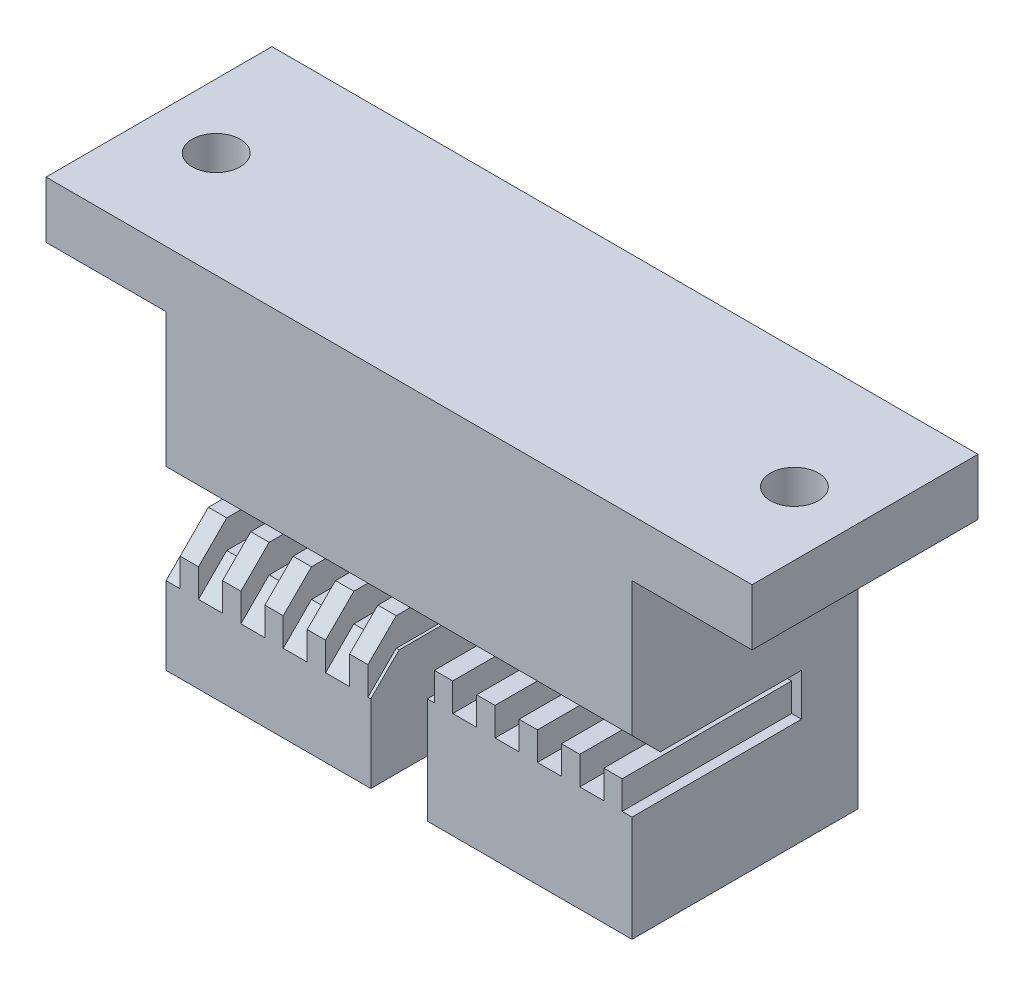
SolidWorks part; units mm, degrees
ref_plane "Front Plane" through (0, 0, 0) normal (0, 0, 1) x (1, 0, 0)
ref_plane "Top Plane" through (0, 0, 0) normal (0, 1, 0) x (1, 0, 0)
ref_plane "Right Plane" through (0, 0, 0) normal (1, 0, 0) x (0, 0, -1)
ref_plane "Plane1" through (0, 0, -1) normal (0, 0, -1) x (-1, 0, 0)
sketch "Sketch1" plane through (0, 0, -1) normal (0, 0, -1) x (-1, 0, 0)
  line L0 (0, 0) -> (50, 0)
  line L1 (50, 0) -> (50, 26)
  line L2 (50, 26) -> (0, 26)
  line L3 (0, 26) -> (0, 0)
extrude "Boss-Extrude1" add sketch "Sketch1" against normal blind 16
sketch "Sketch2" plane through (0, 0, -1) normal (0, 0, -1) x (-1, 0, 0)
  line L0 (41.5, 22) -> (41.5, 0)
  line L1 (41.5, 0) -> (50, 0)
  line L2 (50, 0) -> (50, 22)
  line L3 (50, 22) -> (41.5, 22)
extrude "Cut-Extrude1" cut sketch "Sketch2" against normal through all
sketch "Sketch3" plane through (0, 0, -1) normal (0, 0, -1) x (-1, 0, 0)
  line L0 (0, 0) -> (8.5, 0)
  line L1 (8.5, 0) -> (8.5, 22)
  line L2 (8.5, 22) -> (0, 22)
  line L3 (0, 22) -> (0, 0)
extrude "Cut-Extrude2" cut sketch "Sketch3" against normal through all
sketch "Sketch4" plane through (-41.5, 0, 0) normal (-1, 0, 0) x (0, 0, 1)
  line L0 (15, 10.5) -> (3, 10.5)
  line L1 (3, 10.5) -> (3, 0)
  line L2 (3, 0) -> (15, 0)
  line L3 (15, 0) -> (15, 10.5)
extrude "Cut-Extrude3" cut sketch "Sketch4" against normal through all
sketch "Sketch5" plane through (0, 0, 3) normal (0, 0, 1) x (1, 0, 0)
  line L0 (-23, 7.5) -> (-8.5, 7.5)
  line L1 (-8.5, 7.5) -> (-8.5, 0)
  line L2 (-8.5, 0) -> (-23, 0)
  line L3 (-23, 0) -> (-23, 7.5)
extrude "Boss-Extrude2" add sketch "Sketch5" along normal blind 12
sketch "Sketch6" plane through (0, 0, 3) normal (0, 0, 1) x (1, 0, 0)
  line L0 (-10.5, 9.5) -> (-9.2, 9.5)
  line L1 (-9.2, 9.5) -> (-9.2, 7.5)
  line L2 (-9.2, 7.5) -> (-10.5, 7.5)
  line L3 (-10.5, 7.5) -> (-10.5, 9.5)
extrude "Boss-Extrude3" add sketch "Sketch6" along normal blind 12
sketch "Sketch7" plane through (0, 0, 3) normal (0, 0, 1) x (1, 0, 0)
  line L0 (-12.2, 9.5) -> (-12.2, 7.5)
  line L1 (-12.2, 7.5) -> (-13.5, 7.5)
  line L2 (-13.5, 7.5) -> (-13.5, 9.5)
  line L3 (-13.5, 9.5) -> (-12.2, 9.5)
extrude "Boss-Extrude4" add sketch "Sketch7" along normal blind 12
sketch "Sketch8" plane through (0, 0, 3) normal (0, 0, 1) x (1, 0, 0)
  line L0 (-15.2, 9.5) -> (-15.2, 7.5)
  line L1 (-15.2, 7.5) -> (-16.5, 7.5)
  line L2 (-16.5, 7.5) -> (-16.5, 9.5)
  line L3 (-16.5, 9.5) -> (-15.2, 9.5)
extrude "Boss-Extrude5" add sketch "Sketch8" along normal blind 12
sketch "Sketch9" plane through (0, 0, 3) normal (0, 0, 1) x (1, 0, 0)
  line L0 (-18.2, 9.5) -> (-18.2, 7.5)
  line L1 (-18.2, 7.5) -> (-19.5, 7.5)
  line L2 (-19.5, 7.5) -> (-19.5, 9.5)
  line L3 (-19.5, 9.5) -> (-18.2, 9.5)
extrude "Boss-Extrude6" add sketch "Sketch9" along normal blind 12
sketch "Sketch10" plane through (0, 0, 3) normal (0, 0, 1) x (1, 0, 0)
  line L0 (-21.2, 9.5) -> (-21.2, 7.5)
  line L1 (-21.2, 7.5) -> (-22.5, 7.5)
  line L2 (-22.5, 7.5) -> (-22.5, 9.5)
  line L3 (-22.5, 9.5) -> (-21.2, 9.5)
extrude "Boss-Extrude7" add sketch "Sketch10" along normal blind 12
sketch "Sketch11" plane through (0, 0, 3) normal (0, 0, 1) x (1, 0, 0)
  line L0 (-41.5, 7.5) -> (-27, 7.5)
  line L1 (-27, 7.5) -> (-27, 0)
  line L2 (-27, 0) -> (-41.5, 0)
  line L3 (-41.5, 0) -> (-41.5, 7.5)
extrude "Boss-Extrude8" add sketch "Sketch11" along normal blind 12
sketch "Sketch12" plane through (0, 0, 3) normal (0, 0, 1) x (1, 0, 0)
  line L0 (-27.2, 9.5) -> (-27.2, 7.5)
  line L1 (-27.2, 7.5) -> (-28.5, 7.5)
  line L2 (-28.5, 7.5) -> (-28.5, 9.5)
  line L3 (-28.5, 9.5) -> (-27.2, 9.5)
extrude "Boss-Extrude9" add sketch "Sketch12" along normal blind 12
sketch "Sketch13" plane through (0, 0, 3) normal (0, 0, 1) x (1, 0, 0)
  line L0 (-30.2, 9.5) -> (-30.2, 7.5)
  line L1 (-30.2, 7.5) -> (-31.5, 7.5)
  line L2 (-31.5, 7.5) -> (-31.5, 9.5)
  line L3 (-31.5, 9.5) -> (-30.2, 9.5)
extrude "Boss-Extrude10" add sketch "Sketch13" along normal blind 12
sketch "Sketch14" plane through (0, 0, 3) normal (0, 0, 1) x (1, 0, 0)
  line L0 (-33.2, 9.5) -> (-33.2, 7.5)
  line L1 (-33.2, 7.5) -> (-34.5, 7.5)
  line L2 (-34.5, 7.5) -> (-34.5, 9.5)
  line L3 (-34.5, 9.5) -> (-33.2, 9.5)
extrude "Boss-Extrude11" add sketch "Sketch14" along normal blind 12
sketch "Sketch15" plane through (0, 0, 3) normal (0, 0, 1) x (1, 0, 0)
  line L0 (-36.2, 9.5) -> (-36.2, 7.5)
  line L1 (-36.2, 7.5) -> (-37.5, 7.5)
  line L2 (-37.5, 7.5) -> (-37.5, 9.5)
  line L3 (-37.5, 9.5) -> (-36.2, 9.5)
extrude "Boss-Extrude12" add sketch "Sketch15" along normal blind 12
sketch "Sketch16" plane through (0, 0, 3) normal (0, 0, 1) x (1, 0, 0)
  line L0 (-39.2, 9.5) -> (-39.2, 7.5)
  line L1 (-39.2, 7.5) -> (-40.5, 7.5)
  line L2 (-40.5, 7.5) -> (-40.5, 9.5)
  line L3 (-40.5, 9.5) -> (-39.2, 9.5)
extrude "Boss-Extrude13" add sketch "Sketch16" along normal blind 12
sketch "Sketch17" plane through (0, 26, 0) normal (0, 1, 0) x (-1, 0, 0)
  circle A0 centre (4.5, 7.5) radius 1.7
  dimension "D1" = 7.5
extrude "Cut-Extrude4" cut sketch "Sketch17" against normal through all
sketch "Sketch18" plane through (0, 26, 0) normal (0, 1, 0) x (-1, 0, 0)
  circle A0 centre (45.4494, 7.5) radius 1.7
  dimension "D1" = 7.5
extrude "Cut-Extrude5" cut sketch "Sketch18" against normal through all
chamfer "Chamfer2" distance 2 angle 45 12 edges at (-39.85, 9.5, 15) (-38.35, 7.5, 15) (-36.85, 9.5, 15) (-35.35, 7.5, 15) (-33.85, 9.5, 15) (-32.35, 7.5, 15) (-30.85, 9.5, 15) (-29.35, 7.5, 15) (-27.85, 9.5, 15) (-27.1, 7.5, 15) (-41, 7.5, 15) (-25, 10.5, 15)
